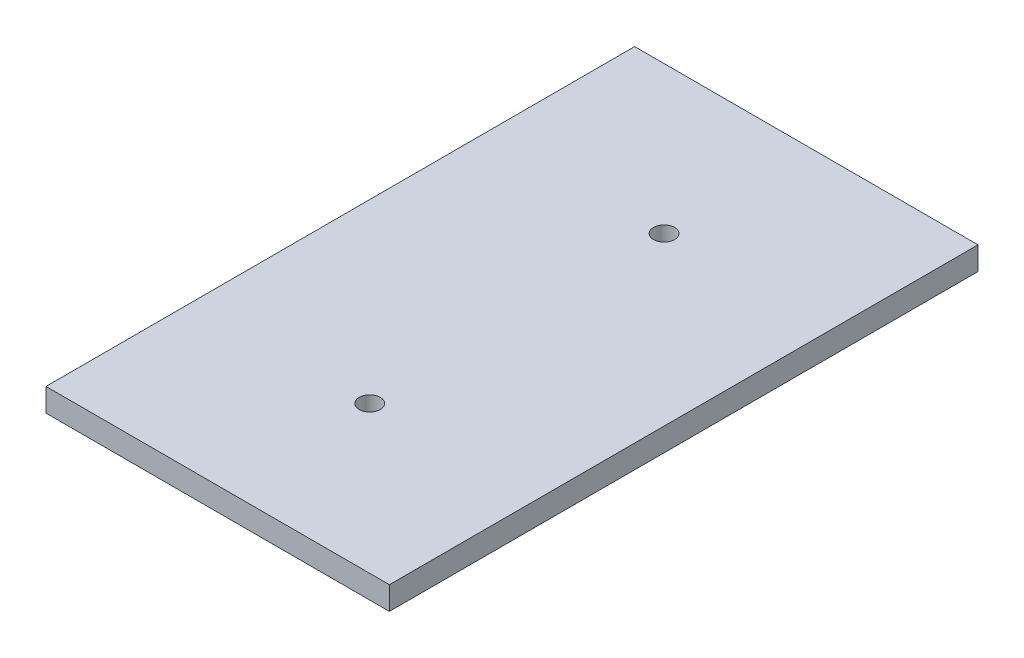
SolidWorks part; units mm, degrees
ref_plane "Front Plane" through (0, 0, 0) normal (0, 0, 1) x (1, 0, 0)
ref_plane "Top Plane" through (0, 0, 0) normal (0, 1, 0) x (1, 0, 0)
ref_plane "Right Plane" through (0, 0, 0) normal (1, 0, 0) x (0, 0, -1)
sketch "Sketch2" plane through (0, 0, 0) normal (0, 1, 0) x (1, 0, 0)
  line L2 (0, 0) -> (0, 152.4)
  line L4 (88.9, 0) -> (88.9, 152.4)
  line L10 (-1000, 76.2) -> (49000, 76.2) construction
  line L13 (0, 152.4) -> (88.9, 152.4)
  line L14 (0, 0) -> (88.9, 0)
  point P11 (0, 76.2)
  dimension "D1" = 152.4
  dimension "D2" = 88.9
extrude "Boss-Extrude1" add sketch "Sketch2" along normal blind 5.9944 contours L4 L13 L2 L14
sketch "Sketch4" plane through (0, 5.9944, 0) normal (0, 1, 0) x (1, 0, 0)
  line L0 (0, 0) -> (0, 152.4) construction
  line L2 (45.72, 114.3) -> (45.72, 38.1) construction
  circle A0 centre (45.72, 114.3) radius 2.7305
  circle A1 centre (45.72, 38.1) radius 2.7305
  point P4 (45.72, 76.2)
  point P12 (0, 76.2)
  dimension "D3" = 5.461
  dimension "D4" = 5.461
  dimension "D1" = 76.2
  dimension "D2" = 45.72
extrude "Cut-Extrude2" cut sketch "Sketch4" against normal through all both
equation "\"threaded_insert_hole\"=0.1472"
equation "\"th\"=1.25249"
